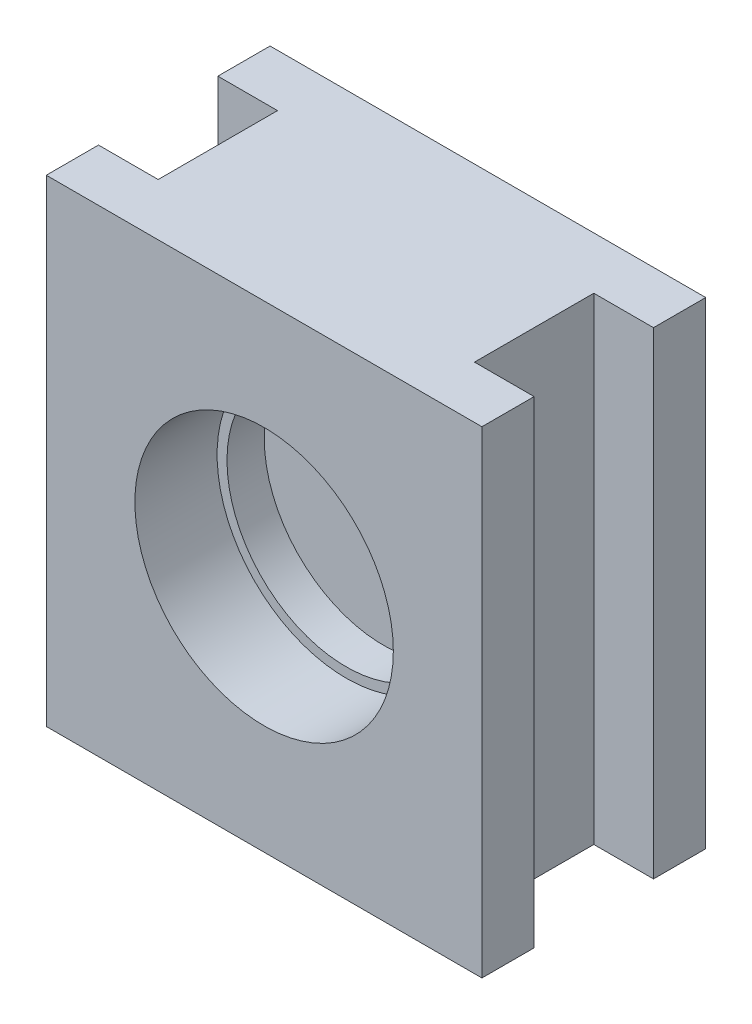
SolidWorks part; units mm, degrees
material "Gray Cast Iron (SN)"
ref_plane "Front Plane" through (0, 0, 0) normal (0, 0, 1) x (1, 0, 0)
ref_plane "Top Plane" through (0, 0, 0) normal (0, 1, 0) x (1, 0, 0)
ref_plane "Right Plane" through (0, 0, 0) normal (1, 0, 0) x (0, 0, -1)
sketch "Sketch1" plane through (0, 0, 0) normal (0, 0, 1) x (1, 0, 0)
  line L1 (13.462, 20.32) -> (-13.462, 20.32)
  line L2 (13.462, 20.32) -> (13.462, -20.32)
  line L3 (13.462, -20.32) -> (-13.462, -20.32)
  line L4 (-13.462, 20.32) -> (-13.462, -20.32)
  line L5 (13.462, 20.32) -> (-13.462, -20.32) construction
  line L6 (13.462, -20.32) -> (-13.462, 20.32) construction
  point P0 (0, 0)
  dimension "D1" = 26.924
  dimension "D2" = 40.64
extrude "Boss-Extrude1" add sketch "Sketch1" along normal blind 19.05
sketch "Sketch2" plane through (13.462, 0, 0) normal (1, 0, 0) x (0, 0, -1)
  line L0 (-19.05, -20.32) -> (0, -20.32) construction
  line L1 (-14.605, -20.32) -> (-4.445, -20.32)
  line L2 (-14.605, -20.32) -> (-14.605, 20.32)
  line L3 (-14.605, 20.32) -> (-4.445, 20.32)
  line L4 (-4.445, -20.32) -> (-4.445, 20.32)
  line L5 (-19.05, 20.32) -> (0, 20.32) construction
  line L6 (-9.525, 20.32) -> (-9.525, -20.32) construction
  line M1 (0, -20.32) -> (0, 20.32)
  line M2 (0, 20.32) -> (-19.05, 20.32)
  line M3 (-19.05, 20.32) -> (-19.05, -20.32)
  line M4 (-19.05, -20.32) -> (0, -20.32)
  dimension "D1" = 10.16
extrude "Boss-Extrude2" add sketch "Sketch2" along normal blind 5.08 contours L2 M4 M2 M3 | L4 M4 M1 M2 region at (13.462, 0, 16.8275) region at (13.462, 0, 2.2225)
mirror "Mirror1" about plane through (0, 0, 0) normal (1, 0, 0) of "Boss-Extrude2"
scale "Scale1" [suppressed]
sketch "Sketch3" plane through (0, 0, 19.05) normal (0, 0, 1) x (1, 0, 0)
  circle A0 centre (0, 0) radius 11
  dimension "D1" = 22
extrude "Cut-Extrude1" cut sketch "Sketch3" against normal blind 7
sketch "Sketch4" plane through (0, 0, 12.05) normal (0, 0, 1) x (1, 0, 0)
  circle A0 centre (0, 0) radius 10.16
  dimension "D1" = 20.32
extrude "Cut-Extrude2" cut sketch "Sketch4" against normal blind 3.175
